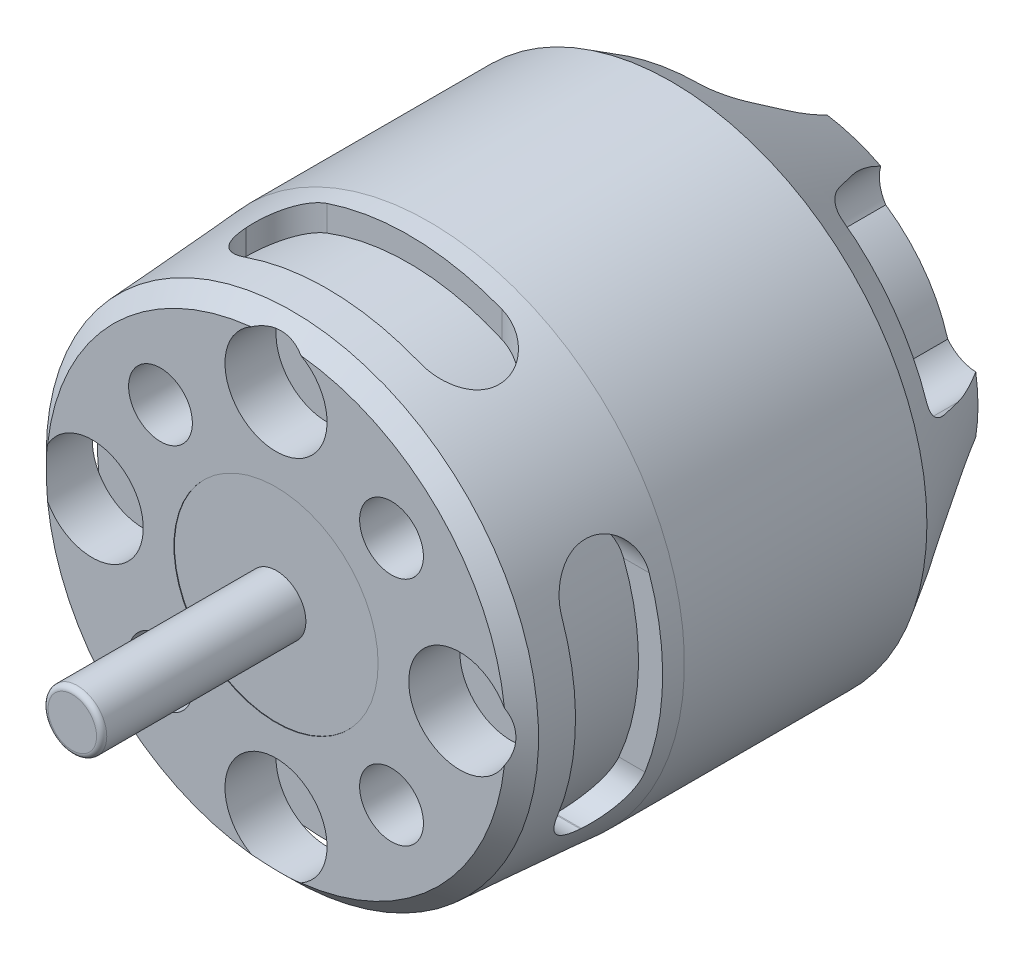
SolidWorks part; units mm, degrees
ref_plane "Front Plane" through (0, 0, 0) normal (0, 0, 1) x (1, 0, 0)
ref_plane "Top Plane" through (0, 0, 0) normal (0, 1, 0) x (1, 0, 0)
ref_plane "Right Plane" through (0, 0, 0) normal (1, 0, 0) x (0, 0, -1)
sketch "Sketch1" plane through (0, 0, 0) normal (0, 0, 1) x (1, 0, 0)
  circle A0 centre (0, 0) radius 12.7
  dimension "D1" = 25.4
extrude "Boss-Extrude1" add sketch "Sketch1" along normal blind 12.065
sketch "Sketch2" plane through (0, 0, 0) normal (0, 0, -1) x (-1, 0, 0)
  circle A0 centre (0, 0) radius 11.43
  dimension "D1" = 22.86
extrude "Cut-Extrude1" cut sketch "Sketch2" against normal blind 12.065
sketch "Sketch4" plane through (0, 0, 0) normal (0, 1, 0) x (1, 0, 0)
  line L0 (12.7, 0) -> (8.89, 6.35)
  line L1 (0, 0) -> (12.7, 0)
  line L2 (0, 0) -> (0, 6.35)
  line L3 (0, 6.35) -> (8.89, 6.35)
  dimension "D1" = 12.7
  dimension "D2" = 6.35
  dimension "D3" = 8.89
revolve "Revolve2" add sketch "Sketch4" angle 360 about L2
sketch "Sketch5" plane through (0, 0, -6.35) normal (0, 0, -1) x (-1, 0, 0)
  line L0 (0, 0) -> (23.0627, 0) construction
  line L1 (7.0472, -7.3048) -> (7.3337, -8.1865)
  line L2 (9.125, 4.445) -> (10.052, 4.445)
  line L3 (-1.4077, -10.0519) -> (-1.1212, -10.9336)
  line L4 (9.125, -4.445) -> (10.052, -4.445)
  line L5 (6.4585, -5.493) -> (-0.7287, -12.1415) construction
  line L6 (7.2199, 4.445) -> (11.322, -4.445) construction
  line L7 (7.22, -4.445) -> (11.3221, 4.445) construction
  line L8 (-1.9964, -8.2402) -> (7.7262, -9.3943) construction
  line L9 (0, 0) -> (7.1268, -21.934) construction
  line L10 (-4.7695, -8.9596) -> (-5.5196, -9.5045)
  line L11 (-9.9949, -1.7674) -> (-10.745, -2.3124)
  line L12 (-3.2284, -7.8399) -> (-11.7724, -3.0589) construction
  line L13 (-8.4538, -0.6477) -> (-6.547, -10.251) construction
  line L14 (0, 0) -> (-18.6582, -13.5559) construction
  line L15 (-9.9949, 1.7674) -> (-10.745, 2.3124)
  line L16 (-4.7695, 8.9596) -> (-5.5196, 9.5045)
  line L17 (-8.4538, 0.6477) -> (-6.547, 10.251) construction
  line L18 (-3.2284, 7.8399) -> (-11.7724, 3.0589) construction
  line L19 (0, 0) -> (-18.6582, 13.5559) construction
  line L20 (-1.4077, 10.0519) -> (-1.1212, 10.9336)
  line L21 (7.0472, 7.3048) -> (7.3337, 8.1865)
  line L22 (-1.9964, 8.2402) -> (7.7262, 9.3943) construction
  line L23 (6.4585, 5.493) -> (-0.7287, 12.1415) construction
  line L24 (0, 0) -> (7.1268, 21.934) construction
  arc A0 (6.8312, 9.635) -> (0.1367, 11.8102) centre (0, 0) ccw
  arc A1 (4.7266, 6.0576) -> (-0.2633, 7.679) centre (0, 0) ccw
  circle A2 centre (0, 0) radius 9.7599 construction
  arc A3 (11.2744, -3.5195) -> (10.052, -4.445) centre (10.052, -3.175) cw
  arc A4 (11.2744, 3.5195) -> (10.052, 4.445) centre (10.052, 3.175) ccw
  arc A5 (9.125, -4.445) -> (7.2218, -2.6234) centre (9.125, -2.54) cw
  arc A6 (7.2218, 2.6234) -> (9.125, 4.445) centre (9.125, 2.54) cw
  arc A7 (4.7266, -6.0576) -> (7.0472, -7.3048) centre (5.2354, -7.8934) cw
  arc A8 (6.8958, -9.5889) -> (7.3337, -8.1865) centre (6.1259, -8.5789) ccw
  arc A9 (0.1367, -11.8102) -> (-1.1212, -10.9336) centre (0.0866, -10.5412) cw
  arc A10 (-1.4077, -10.0519) -> (-0.2633, -7.679) centre (0.4041, -9.4632) cw
  arc A11 (-4.3006, -6.3672) -> (-4.7695, -8.9596) centre (-5.8893, -7.4184) cw
  arc A12 (-6.9887, -9.5214) -> (-5.5196, -9.5045) centre (-6.2661, -8.4771) ccw
  arc A13 (-11.215, -3.7044) -> (-10.745, -2.3124) centre (-9.9985, -3.3398) cw
  arc A14 (-9.9949, -1.7674) -> (-7.3845, -2.1225) centre (-8.8752, -3.3086) cw
  arc A15 (-7.3845, 2.1225) -> (-9.9949, 1.7674) centre (-8.8752, 3.3086) cw
  arc A16 (-11.215, 3.7044) -> (-10.745, 2.3124) centre (-9.9985, 3.3398) ccw
  arc A17 (-6.9887, 9.5214) -> (-5.5196, 9.5045) centre (-6.2661, 8.4771) cw
  arc A18 (-4.7695, 8.9596) -> (-4.3006, 6.3672) centre (-5.8893, 7.4184) cw
  arc A19 (-0.2633, 7.679) -> (-1.4077, 10.0519) centre (0.4041, 9.4632) cw
  arc A20 (0.1367, 11.8102) -> (-1.1212, 10.9336) centre (0.0866, 10.5412) ccw
  arc A21 (6.8312, 9.635) -> (7.3337, 8.1865) centre (6.1259, 8.5789) cw
  arc A22 (7.0472, 7.3048) -> (4.7266, 6.0576) centre (5.2354, 7.8934) cw
  arc A23 (7.2218, -2.6234) -> (7.2218, 2.6234) centre (0, 0) ccw
  arc A24 (11.2744, -3.5195) -> (11.2744, 3.5195) centre (0, 0) ccw
  arc A25 (0.1367, -11.8102) -> (6.8958, -9.5889) centre (0, 0) ccw
  arc A26 (-0.2633, -7.679) -> (4.7266, -6.0576) centre (0, 0) ccw
  arc A27 (-7.3845, -2.1225) -> (-4.3006, -6.3672) centre (0, 0) ccw
  arc A28 (-11.215, -3.7044) -> (-6.9887, -9.5214) centre (0, 0) ccw
  arc A29 (-4.3006, 6.3672) -> (-7.3845, 2.1225) centre (0, 0) ccw
  arc A30 (-6.9887, 9.5214) -> (-11.215, 3.7044) centre (0, 0) ccw
  point P5 (9.271, 0)
  point P93 (0, 0)
  dimension "D1" = 15.367
  dimension "D2" = 23.622
  dimension "D3" = 19.5199
  dimension "D5" = 1.27
  dimension "D6" = 1.905
  dimension "D9" = 5.2468
  dimension "D4" = 8.89
  dimension "D7" = 4.445
  dimension "D8" = 9.271
  dimension "D10" = 3.5195
  dimension "D11" = 3.5195
  dimension "D12" = 2.6234
  dimension "D13" = 5
extrude "Cut-Extrude2" cut sketch "Sketch5" against normal blind 12.065
sketch "Sketch6" plane through (0, 0, 0) normal (0, 1, 0) x (1, 0, 0)
  line L0 (12.192, -19.685) -> (12.7, -12.065)
  line L1 (12.7, -12.065) -> (0, -12.065)
  line L3 (12.192, -19.685) -> (0, -19.685)
  line L4 (0, -12.065) -> (0, -19.685)
  line L5 (12.7, -12.065) -> (12.7117, -11.9521)
  dimension "D1" = 12.192
  dimension "D2" = 0
  dimension "D3" = 7.62
revolve "Revolve3" add sketch "Sketch6" angle 360 about L4
ref_plane "Plane1" through (0, 12.7, 0) normal (0, 1, 0) x (1, 0, 0)
sketch "Sketch7" plane through (0, 12.7, 0) normal (0, 1, 0) x (1, 0, 0)
  line L0 (0.2857, 0.8146) -> (0.2857, -28.3698) construction
  line L1 (-12.192, -19.685) -> (12.192, -19.685) construction
  line L2 (4.6291, -13.081) -> (-4.0577, -13.081)
  line L3 (6.6357, -15.0876) -> (6.6357, -15.1384)
  line L4 (4.6291, -17.145) -> (-4.0577, -17.145)
  line L5 (-6.0643, -15.0876) -> (-6.0643, -15.1384)
  line L6 (6.6357, -13.081) -> (-6.0643, -17.145) construction
  line L7 (6.6357, -17.145) -> (-6.0643, -13.081) construction
  line L8 (12.7, -12.065) -> (-12.7, -12.065) construction
  arc A0 (-4.0577, -13.081) -> (-6.0643, -15.0876) centre (-4.0577, -15.0876) ccw
  arc A1 (-6.0643, -15.1384) -> (-4.0577, -17.145) centre (-4.0577, -15.1384) ccw
  arc A2 (4.6291, -17.145) -> (6.6357, -15.1384) centre (4.6291, -15.1384) ccw
  arc A3 (6.6357, -15.0876) -> (4.6291, -13.081) centre (4.6291, -15.0876) ccw
  point P1 (0.2857, -15.113)
  dimension "D4" = 2.0066
  dimension "D1" = 2.54
  dimension "D2" = 1.016
  dimension "D3" = 12.7
extrude "Cut-Extrude3" cut sketch "Sketch7" against normal through all
ref_plane "Plane2" through (12.7, 0, 0) normal (1, 0, 0) x (0, 0, -1)
pattern_circular "CirPattern1" count 2 every 90 about axis through (0, 0, 19.685) along (0, 0, -1) of "Cut-Extrude3"
sketch "Sketch9" plane through (0, 0, 19.685) normal (0, 0, 1) x (1, 0, 0)
  line L0 (0, 0) -> (9.4282, 9.4282) construction
  line L1 (0, 0) -> (0, 3.9507) construction
  circle A0 centre (0, 0) radius 5.08
  circle A1 centre (0, 9.144) radius 2.54
  circle A2 centre (9.144, 0) radius 2.54
  circle A3 centre (0, -9.144) radius 2.54
  circle A4 centre (-9.144, 0) radius 2.54
  circle A5 centre (5.7474, 5.7474) radius 1.5875
  circle A6 centre (5.7474, -5.7474) radius 1.5875
  circle A7 centre (-5.7474, -5.7474) radius 1.5875
  circle A8 centre (-5.7474, 5.7474) radius 1.5875
  point P14 (0, 0)
  point P27 (0, 0)
  dimension "D1" = 10.16
  dimension "D2" = 5.08
  dimension "D6" = 3.175
  dimension "D3" = 9.144
  dimension "D5" = 45
  dimension "D7" = 8.128
  dimension "D4" = 4
  dimension "D8" = 4
extrude "Cut-Extrude4" cut sketch "Sketch9" against normal blind 5.08 contours A7 | A4 | A8 | A1 | A5 | A2 | A6 | A3 region at (0, 9.144, 19.685) region at (9.144, 0, 19.685) region at (0, -9.144, 19.685) region at (-9.144, 0, 19.685) region at (5.7474, 5.7474, 19.685) region at (5.7474, -5.7474, 19.685) region at (-5.7474, -5.7474, 19.685) region at (-5.7474, 5.7474, 19.685)
extrude "Cut-Extrude5" cut sketch "Sketch9<3>" against normal blind 0.0254 contours A0 region at (0, 0, 19.685)
sketch "Sketch9<3>" plane through (0, 0, 19.685) normal (0, 0, 1) x (1, 0, 0) same geometry as "Sketch9"
sketch "Sketch10" plane through (0, 0, 19.6596) normal (0, 0, 1) x (1, 0, 0)
  circle A0 centre (0, 0) radius 1.4605
  dimension "D1" = 2.921
extrude "Boss-Extrude2" add sketch "Sketch10" along normal blind 10.16
chamfer "Chamfer1" distance 0.762 angle 45 1 edges at (-12.192, 0, 19.685) tangent propagation no first distance on face at (5.08, 0, 19.685)
fillet "Fillet1" radius 0.254 1 edges at (1.4605, 0, 29.8196) type face fillet first side face at (1.4605, 0, 29.8196) second side face at (1.4605, 0, 29.8196)
extrude "Boss-Extrude3" add sketch "Sketch10<2>" against normal blind 26.67
sketch "Sketch10<2>" plane through (0, 0, 19.6596) normal (0, 0, 1) x (1, 0, 0) same geometry as "Sketch10"
fillet "Fillet2" radius 0.254 1 edges at (1.4605, 0, -7.0104) type face fillet first side face at (-1.4605, 0, -6.35) second side face at (1.4605, 0, -7.0104)
sketch "Sketch12" plane through (0, 0, 17.145) normal (0, 0, -1) x (-1, 0, 0)
  circle A0 centre (0, 0) radius 11.43
  dimension "D1" = 22.86
extrude "Boss-Extrude5" add sketch "Sketch12" along normal blind 15.24
